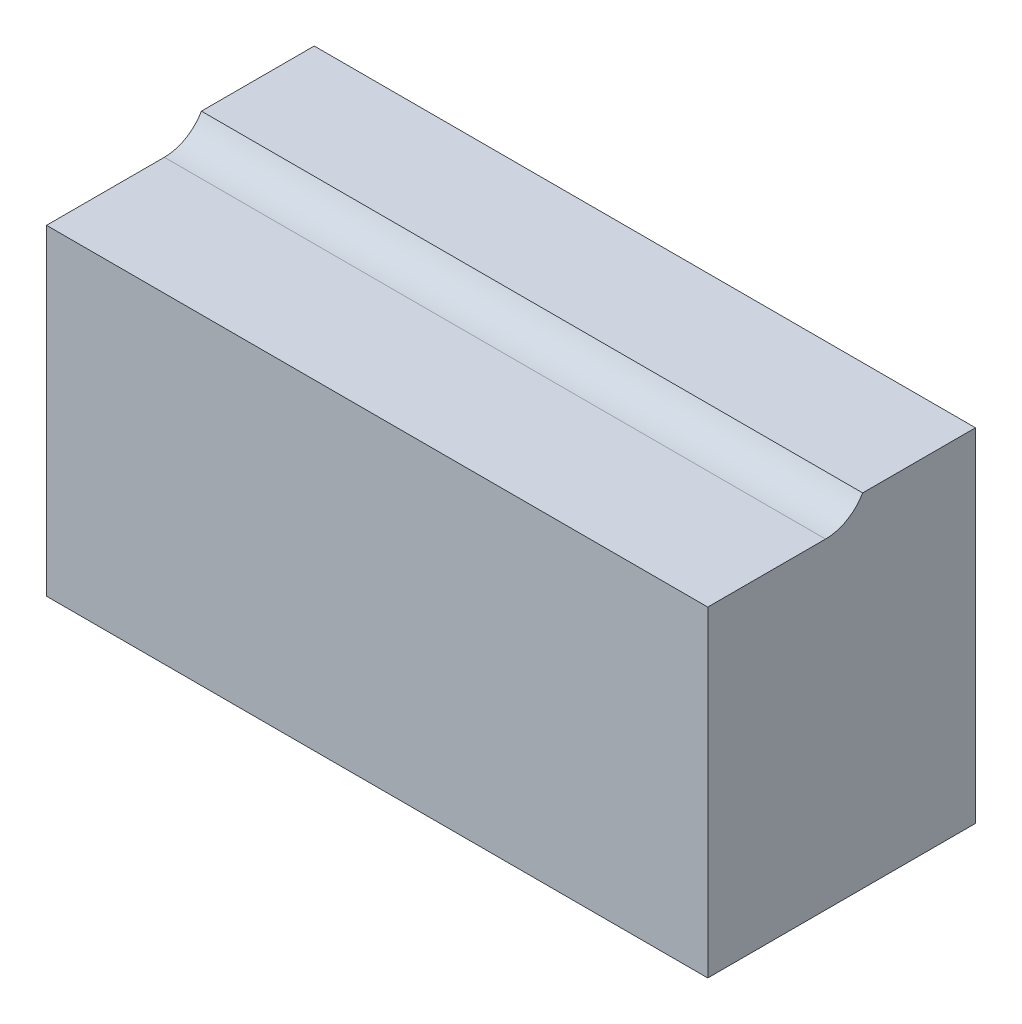
SolidWorks part; units mm, degrees
material "K110"
ref_plane "Front Plane" through (0, 0, 0) normal (0, 0, 1) x (1, 0, 0)
ref_plane "Top Plane" through (0, 0, 0) normal (0, 1, 0) x (1, 0, 0)
ref_plane "Right Plane" through (0, 0, 0) normal (1, 0, 0) x (0, 0, -1)
sketch "Sketch1" plane through (0, 0, 0) normal (0, 0, 1) x (1, 0, 0)
  line L1 (5.7154, -38) -> (67.4654, -38)
  line L2 (5.7154, -38) -> (5.7154, 0)
  line L3 (5.7154, 0) -> (67.4654, 0)
  line L4 (67.4654, -38) -> (67.4654, 0)
  dimension "D1" = 38
  dimension "D2" = 61.75
extrude "Boss-Extrude1" add sketch "Sketch1" along normal mid plane 25
sketch "Sketch2" plane through (67.4654, 0, 0) normal (1, 0, 0) x (0, 0, -1)
  line L0 (1.9641, -6) -> (12.5, -6)
  line L1 (12.5, -38) -> (12.5, 0) construction
  line L2 (12.5, -6) -> (12.5, 0)
  line L3 (12.5, 0) -> (-12.5, 0)
  line L4 (-12.5, 0) -> (-12.5, -8)
  line L5 (-12.5, -38) -> (-12.5, 0) construction
  line L6 (-12.5, -8) -> (-1.5, -8)
  line L7 (-12.5, -38) -> (12.5, -38) construction
  arc A0 (-1.5, -8) -> (-5.4392, -4.6946) centre (-1.5, -4) ccw construction
  arc A1 (-1.5, -8) -> (1.9641, -6) centre (-1.5, -4) ccw
  dimension "D1" = 32
extrude "Cut-Extrude1" cut sketch "Sketch2" against normal up to next
hole_wizard "M6 Tapped Hole1" positions "Sketch5" profile "Sketch4" tap size "M6" standard "ISO"
sketch "Sketch5" plane through (0, -38, 0) normal (0, -1, 0) x (-1, 0, 0)
  line L0 (-67.4654, 0) -> (-5.7154, 0) construction
  line L1 (-67.4654, -12.5) -> (-67.4654, 12.5) construction
  line L2 (-5.7154, 12.5) -> (-5.7154, -12.5) construction
  line L4 (-36.5904, 12.5) -> (-36.5904, -12.5) construction
  line L5 (-67.4654, 12.5) -> (-5.7154, 12.5) construction
  line L6 (-5.7154, -12.5) -> (-67.4654, -12.5) construction
  point P0 (-15.5904, 0)
  point P2 (-57.5904, 0)
  dimension "D1" = 42
sketch "Sketch4" plane through (15.5904, -38, 0) normal (1, 0, 0) x (0, 0, -1)
  line L0 (0, 0) -> (0, 18.5022)
  line L1 (0, 18.5022) -> (2.5, 17)
  line L2 (2.5, 17) -> (2.5, 0)
  line L5 (2.5, 0) -> (0, 0)
  line L10 (0, 18.5022) -> (-2.5, 17) construction
  line L11 (0, -6.35) -> (0, 107.95) construction
  dimension "Tap Drill Dia." = 5
  dimension "Tap Drill Depth" = 17
  dimension "Drill Angle" = 118
cosmetic thread "Hole Thread1"
cosmetic thread "Hole Thread2"
